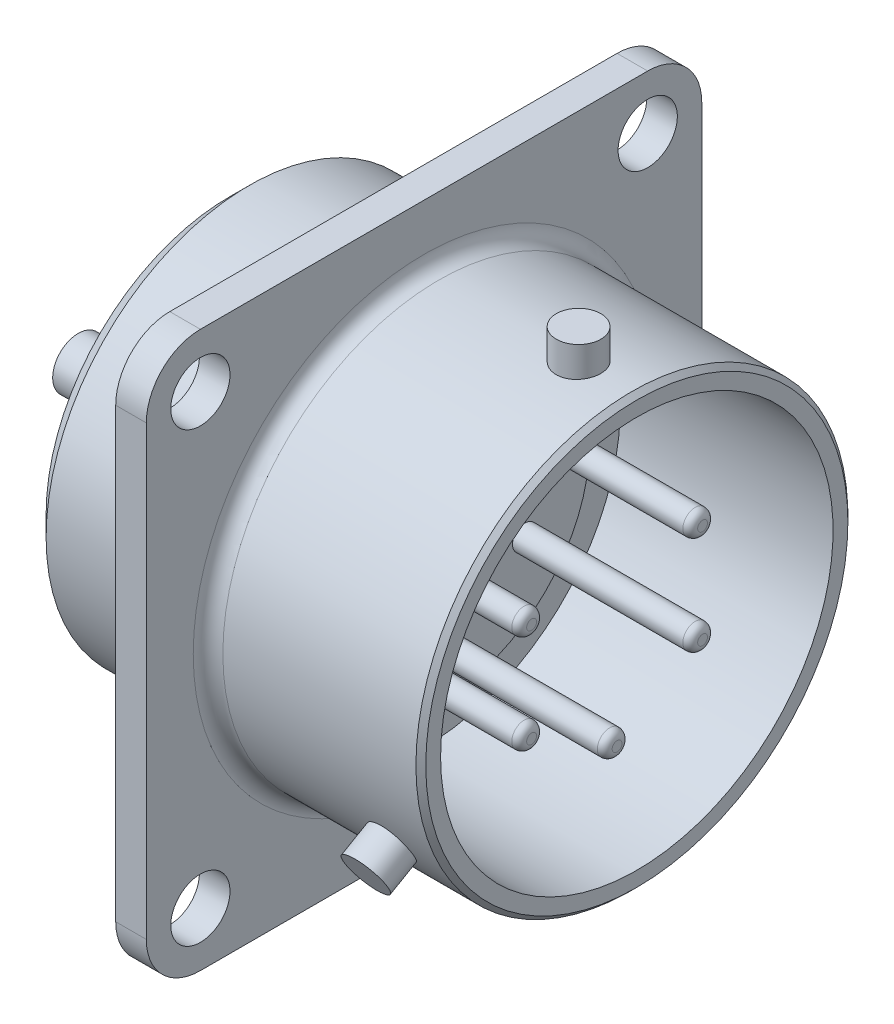
SolidWorks part; units mm, degrees
material "ASTM A36 Steel"
ref_plane "Front Plane" through (0, 0, 0) normal (0, 0, 1) x (1, 0, 0)
ref_plane "Top Plane" through (0, 0, 0) normal (0, 1, 0) x (1, 0, 0)
ref_plane "Right Plane" through (0, 0, 0) normal (1, 0, 0) x (0, 0, -1)
ref_axis "Axis1" through (-12.0345, 0, 0) along (1, 0, 0)
sketch "Sketch1" plane through (0, 0, 0) normal (0, 0, 1) x (1, 0, 0)
  line L0 (1.5748, 11.8745) -> (1.5748, 36.5125)
  line L1 (1.5748, 36.5125) -> (0, 36.5125)
  line L2 (0, 36.5125) -> (0, 10.8331)
  line L3 (2.3622, 7.7343) -> (1.5748, 7.7343)
  line L4 (1.5748, 7.7343) -> (1.5748, 10.0965)
  line L6 (-8.4328, 9.4361) -> (-8.4328, 0)
  line L7 (-8.4328, 0) -> (2.3622, 0)
  line L8 (12.5222, 10.0965) -> (12.5222, 10.8585)
  line L9 (12.2682, 11.1125) -> (2.3368, 11.1125)
  line L10 (25.6286, 0) -> (36.7411, 0) construction
  line L11 (-8.4328, 9.4361) -> (-7.4168, 10.4521)
  line L12 (-7.4168, 10.4521) -> (-0.381, 10.4521)
  line L13 (12.2682, 11.1125) -> (12.5222, 10.8585)
  line L15 (12.5222, 10.0965) -> (1.5748, 10.0965)
  line L16 (2.3622, 7.7343) -> (2.3622, 0)
  arc A0 (2.3368, 11.1125) -> (1.5748, 11.8745) centre (2.3368, 11.8745) cw
  arc A1 (-0.381, 10.4521) -> (0, 10.8331) centre (-0.381, 10.8331) ccw
  point P11 (-11.811, 0)
  dimension "D14" = 0.762
  dimension "D18" = 0.381
  dimension "D2" = 0.254
  dimension "D3" = 20.955
  dimension "D4" = 1.5748
  dimension "D5" = 10.9474
  dimension "D6" = 25.4
  dimension "D7" = 22.225
  dimension "D8" = 20.9042
  dimension "D9" = 45
  dimension "D10" = 12.5222
  dimension "D11" = 20.193
  dimension "D12" = 1.016
  dimension "D13" = 45
  dimension "D15" = 15.4686
  dimension "D16" = 10.16
  dimension "D17" = 2.3622
  dimension "D19" = 1.016
  dimension "D20" = 11.811
revolve "BR-00 Body Revolve" add sketch "Sketch1" angle 360 about L10
sketch "Sketch2" plane through (0, 0, 0) normal (1, 0, 0) x (0, 0, -1)
  line L1 (-11.5062, 14.2875) -> (11.5062, 14.2875)
  line L2 (-11.5062, -14.2875) -> (11.5062, -14.2875)
  line L3 (-14.2875, 11.5062) -> (-14.2875, -11.5062)
  line L4 (14.2875, 11.5062) -> (14.2875, -11.5062)
  arc A0 (11.5062, 14.2875) -> (14.2875, 11.5062) centre (11.5062, 11.5062) cw
  circle A1 centre (11.5062, 11.5062) radius 1.524
  circle A2 centre (11.5062, -11.5062) radius 1.524
  arc A3 (11.5062, -14.2875) -> (14.2875, -11.5062) centre (11.5062, -11.5062) ccw
  arc A4 (-11.5062, -14.2875) -> (-14.2875, -11.5062) centre (-11.5062, -11.5062) cw
  circle A5 centre (-11.5062, -11.5062) radius 1.524
  circle A6 centre (-11.5062, 11.5062) radius 1.524
  arc A7 (-11.5062, 14.2875) -> (-14.2875, 11.5062) centre (-11.5062, 11.5062) ccw
  point P0 (14.2875, 0)
  point P4 (0, 14.2875)
  dimension "D1" = 2.7813
  dimension "D6" = 3.048
  dimension "D3" = 23.0124
  dimension "D2" = 28.575
extrude "CE-00 Body Flange" cut sketch "Sketch2" along normal up to surface (1.5748 mm away) flip side to cut up to face at (1.5748, 0, 36.5125)
sketch "Sketch5" plane through (0, 0, 0) normal (0, 0, 1) x (1, 0, 0)
  line L0 (9.525, 12.6365) -> (9.525, -12.1024) construction
  line L1 (9.525, 10.6045) -> (10.668, 10.6045)
  line L2 (9.525, 10.6045) -> (9.525, 12.6365)
  line L3 (9.525, 12.6365) -> (10.668, 12.6365)
  line L4 (10.668, 10.6045) -> (10.668, 12.6365)
  line L6 (12.2682, 11.1125) -> (2.3368, 11.1125) construction
  dimension "D1" = 2.286
  dimension "D2" = 1.524
  dimension "D3" = 9.525
  dimension "D4" = 2.032
revolve "BR-00 Bayonete Pin" add sketch "Sketch5" angle 360 about L0
pattern_circular "CP-00 Bayonete Pins" count 3 over 360 about axis through (-12.0345, 0, 0) along (1, 0, 0) of "BR-00 Bayonete Pin"
sketch "Sketch3" plane through (-8.4328, 0, 0) normal (-1, 0, 0) x (0, 0, 1)
  line L0 (1.4749, 0) -> (4.4076, 0) construction
  line L1 (4.3994, 2.54) -> (2.5548, 1.475) construction
  circle A0 centre (4.3994, 2.54) radius 1.3208
  circle A1 centre (4.3994, 2.54) radius 0.8128
  dimension "D1" = 2.6416
  dimension "D4" = 0.508
  dimension "D2" = 5.08
  dimension "D3" = 30
extrude "BE-00 Terminal" add sketch "Sketch3" along normal up to vertex (3.3782 mm away) up to point (-11.811, 0, 0)
pattern_circular "CP-00 Terminal" count 6 over 360 about axis through (-12.0345, 0, 0) along (1, 0, 0) skipping 5 of "BE-00 Terminal"
sketch "Sketch8" plane through (2.3622, 0, 0) normal (1, 0, 0) x (0, 0, -1)
  circle A0 centre (-4.3994, 2.54) radius 0.7938
  dimension "D2" = 1.5875
extrude "CE-00 Sockets" [suppressed] cut sketch "Sketch8" against normal blind 10.16
pattern_circular "CP-00 Sockets" [suppressed] count 6 over 360 about axis through (-12.0345, 0, 0) along (1, 0, 0) of bodies 110
sketch "Sketch9" plane through (2.3622, 0, 0) normal (1, 0, 0) x (0, 0, -1)
  circle A0 centre (-4.3994, 2.54) radius 0.635
  dimension "D1" = 1.27
extrude "Boss-Extrude1" add sketch "Sketch9" along normal offset from surface (9.144 mm away) 1.016 up to face at (12.5222, 0, 10.8585)
fillet "Fillet1" radius 0.381 1 edges at (11.5062, 2.54, 5.0344)
pattern_circular "CirPattern1" count 6 over 360 about axis through (-12.0345, 0, 0) along (1, 0, 0) skipping 5 of "Boss-Extrude1", "Fillet1"
